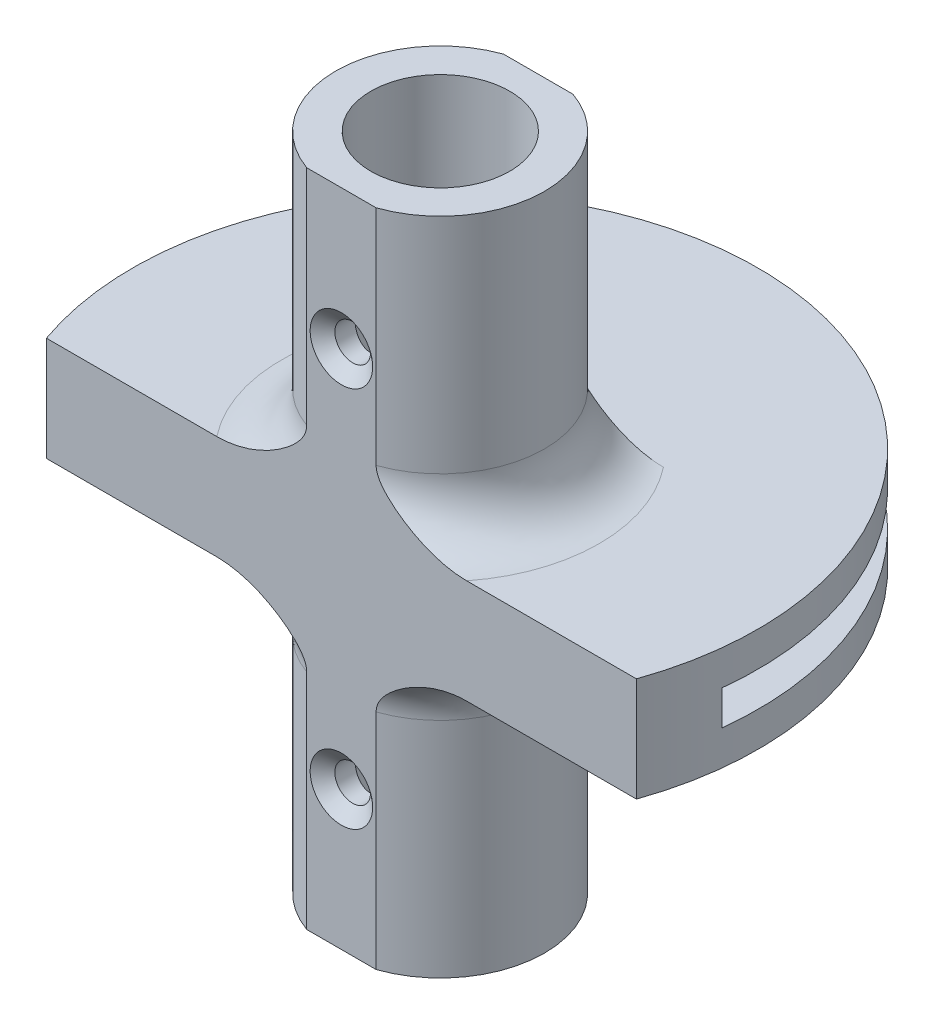
SolidWorks part; units mm, degrees
other "Camera1"
material "ABS"
ref_plane "Front Plane" through (0, 0, 0) normal (0, 0, 1) x (1, 0, 0)
ref_plane "Top Plane" through (0, 0, 0) normal (0, 1, 0) x (1, 0, 0)
ref_plane "Right Plane" through (0, 0, 0) normal (1, 0, 0) x (0, 0, -1)
sketch "Sketch3" plane through (0, 0, 0) normal (0, 1, 0) x (1, 0, 0)
  line L8 (0, 28.6) -> (0, -28.6) construction
  line L9 (0, 28.6) -> (0, -9.5) construction
  line L10 (-26.976, -9.5) -> (26.976, -9.5)
  line L11 (-28.4259, -3.15) -> (28.4259, -3.15)
  arc A4 (26.976, -9.5) -> (-26.976, -9.5) centre (0, 0) ccw
  dimension "D1" = 38.1
  dimension "D2" = 6.35
extrude "Boss-Extrude1" add sketch "Sketch3" along normal blind 3.175 contours L11 A4 | L10 A4 L11
sketch "Sketch18" plane through (0, 0, 0) normal (0, 1, 0) x (1, 0, 0)
  line L0 (7.6093, 9.5806) -> (7.6093, 23.8709)
  line L1 (7.6093, 23.8709) -> (-6.6782, 23.848)
  line L2 (-6.6782, 23.848) -> (-6.6782, 9.5577)
  line L3 (-6.6782, 9.5577) -> (7.6093, 9.5806)
  line L4 (3.4908, 13.6518) -> (3.4908, 19.7615)
  line L5 (3.4908, 19.7615) -> (-4.6572, 19.7686)
  line L6 (-4.6572, 19.7686) -> (-4.6572, 21.7998)
  line L7 (-4.6572, 21.7998) -> (-2.6268, 21.7998)
  line L8 (-2.6268, 21.7998) -> (-2.6269, 11.6094)
  line L9 (-2.6269, 11.6094) -> (-4.6581, 11.6094)
  line L10 (-4.6581, 11.6094) -> (-4.6581, 13.6399)
  line L11 (-4.6581, 13.6399) -> (3.4908, 13.6518)
  spline S0 degree 3 poles (7.6093, 9.5806) (2.8493, 9.573) (-1.9139, 9.5653) (-6.6782, 9.5577) knots 3 3 3 3 4 4 4 4
  spline S1 degree 3 poles (7.6093, 23.8709) (7.6093, 19.1093) (7.6093, 14.3449) (7.6093, 9.5806) knots 2 2 2 2 3 3 3 3
  spline S2 degree 3 poles (-6.6782, 23.848) (-1.9179, 23.8556) (2.8435, 23.8632) (7.6093, 23.8709) knots 1 1 1 1 2 2 2 2
  spline S3 degree 3 poles (-6.6782, 9.5577) (-6.6782, 14.3202) (-6.6782, 19.0827) (-6.6782, 23.848) knots 0 0 0 0 1 1 1 1
  spline S4 degree 3 poles (3.4908, 19.7615) (3.4639, 19.7638) (3.4462, 19.7666) (3.4285, 19.7666) (1.4101, 19.7661) (-0.6084, 19.7654) (-2.6268, 19.7647) knots 12 12 12 12 13 13 13 14 14 14 14
  spline S5 degree 3 poles (3.4908, 13.6518) (3.4908, 15.6921) (3.4908, 17.7258) (3.4908, 19.7615) knots 11 11 11 11 12 12 12 12
  spline S6 degree 3 poles (-2.6269, 13.6437) (-0.6039, 13.6431) (1.419, 13.6424) (3.442, 13.6422) (3.4587, 13.6422) (3.4754, 13.6486) (3.4908, 13.6518) knots 9 9 9 9 10 10 10 11 11 11 11
  spline S7 degree 3 poles (-2.6269, 11.6094) (-2.6269, 12.2941) (-2.6269, 12.9689) (-2.6269, 13.6437) knots 8 8 8 8 9 9 9 9
  spline S8 degree 3 poles (-4.6581, 11.6094) (-3.9766, 11.6094) (-3.3042, 11.6094) (-2.6269, 11.6094) knots 7 7 7 7 8 8 8 8
  spline S9 degree 3 poles (-4.6581, 13.6399) (-4.6581, 12.9525) (-4.6581, 12.2802) (-4.6581, 11.6094) knots 6 6 6 6 7 7 7 7
  spline S10 degree 3 poles (-2.623, 13.6399) (-3.3011, 13.6399) (-3.9791, 13.6399) (-4.6581, 13.6399) knots 5 5 5 5 6 6 6 6
  spline S11 degree 3 poles (-2.6229, 19.7686) (-2.623, 17.7257) (-2.623, 15.6828) (-2.623, 13.6399) knots 4 4 4 4 5 5 5 5
  spline S12 degree 3 poles (-4.6572, 19.7686) (-3.9725, 19.7686) (-3.2977, 19.7686) (-2.6229, 19.7686) knots 3 3 3 3 4 4 4 4
  spline S13 degree 3 poles (-4.6572, 21.7998) (-4.6572, 21.1183) (-4.6572, 20.4459) (-4.6572, 19.7686) knots 2 2 2 2 3 3 3 3
  spline S14 degree 3 poles (-2.6268, 21.7998) (-3.3141, 21.7998) (-3.9864, 21.7998) (-4.6572, 21.7998) knots 1 1 1 1 2 2 2 2
  spline S15 degree 3 poles (-2.6268, 19.7647) (-2.6268, 20.4427) (-2.6268, 21.1208) (-2.6268, 21.7998) knots 0 0 0 0 1 1 1 1
sketch "Sketch19" plane through (0, 0, 0) normal (0, 1, 0) x (1, 0, 0)
  line L3 (-3.175, 8.4947) -> (3.175, 8.4947)
  line L4 (-3.175, -9.5) -> (3.175, -9.5)
  arc A3 (3.175, -9.5) -> (3.175, 8.4947) centre (0.0442, -0.5026) ccw
  arc A4 (-3.175, 8.4947) -> (-3.175, -9.5) centre (0.0442, -0.5026) ccw
  circle A5 centre (0.0442, -0.5026) radius 6.35
  point P10 (0, 8.4947)
  point P11 (0, -9.5)
  dimension "D1" = 12.7
  dimension "D2" = 3.1765
  dimension "D3" = 3.2059
  dimension "D4" = 6.35
extrude "Boss-Extrude2" add sketch "Sketch19" against normal blind 25.4 contours L3 A4 A5 | L3 A5 L4 A3 region at (0, 0, -8.2324)
ref_plane "Plane2" through (0, 3.175, 0) normal (0, 1, 0) x (1, 0, 0)
sketch "Sketch20" plane through (0, 3.175, 0) normal (0, 1, 0) x (1, 0, 0)
  line L0 (-28.4259, -3.15) -> (28.4259, -3.15) construction
  line L1 (-26.976, -9.5) -> (26.976, -9.5) construction
  line L2 (-28.4259, -3.15) -> (28.4259, -3.15)
  line L3 (-26.976, -9.5) -> (26.976, -9.5)
  arc A0 (26.976, -9.5) -> (-26.976, -9.5) centre (0, 0) ccw construction
  arc A1 (26.976, -9.5) -> (28.4259, -3.15) centre (0, 0) ccw
  arc A2 (-28.4259, -3.15) -> (-26.976, -9.5) centre (0, 0) ccw
extrude "Boss-Extrude3" add sketch "Sketch20" along normal blind 3.175
ref_plane "Plane3" through (0, 6.35, 0) normal (0, 1, 0) x (1, 0, 0)
sketch "Sketch21" plane through (0, 6.35, 0) normal (0, 1, 0) x (1, 0, 0)
  line L0 (-26.976, -9.5) -> (26.976, -9.5)
  arc A0 (26.976, -9.5) -> (-26.976, -9.5) centre (0, 0) ccw construction
  arc A1 (26.976, -9.5) -> (-26.976, -9.5) centre (0, 0) ccw
extrude "Boss-Extrude4" add sketch "Sketch21" along normal blind 3.175
ref_plane "Plane4" through (0, 9.525, 0) normal (0, 1, 0) x (1, 0, 0)
sketch "Sketch23" plane through (0, 9.525, 0) normal (0, 1, 0) x (1, 0, 0)
  line L0 (-26.976, -9.5) -> (26.976, -9.5) construction
  line L1 (-3.175, 8.4947) -> (3.175, 8.4947) construction
  line L2 (-3.175, -9.5) -> (3.175, -9.5)
  line L3 (-3.175, 8.4947) -> (3.175, 8.4947)
  circle A0 centre (0.0442, -0.5026) radius 6.35 construction
  arc A1 (-3.175, 8.4947) -> (-3.175, -9.5) centre (0.0442, -0.5026) ccw construction
  arc A2 (3.175, -9.5) -> (3.175, 8.4947) centre (0.0442, -0.5026) ccw construction
  circle A3 centre (0.0442, -0.5026) radius 6.35
  arc A4 (-3.175, 8.4947) -> (-3.175, -9.5) centre (0.0442, -0.5026) ccw
  arc A5 (3.175, -9.5) -> (3.175, 8.4947) centre (0.0442, -0.5026) ccw
extrude "Boss-Extrude5" add sketch "Sketch23" along normal blind 25.4
hole_wizard "CSK for #4 Flat Head Machine Screw (100)1" positions "Sketch24" profile "Sketch25" countersink size "#4" standard "ANSI Inch" end condition up to next
sketch "Sketch24" plane through (0, 0, 9.5) normal (0, 0, 1) x (1, 0, 0)
  line L4 (0, -25.4) -> (0, 0) construction
  line L5 (-3.175, -25.4) -> (3.175, -25.4) construction
  line L7 (0, 9.433) -> (0, 34.925) construction
  line L8 (-3.175, 34.925) -> (3.175, 34.925) construction
  point P0 (0, -12.7)
  point P2 (0, 22.179)
sketch "Sketch25" plane through (0, -12.7, 9.5) normal (1, 0, 0) x (0, -1, 0)
  line L0 (0, 0) -> (0, 2.6475)
  line L1 (0, 2.6475) -> (1.6319, 2.6475)
  line L2 (1.6319, 2.6475) -> (1.6319, 1.0284)
  line L3 (1.6319, 1.0284) -> (2.8575, 0)
  line L5 (2.8575, 0) -> (0, 0)
  line L6 (-1.632, 1.0284) -> (-2.8575, 0) construction
  line L11 (0, -6.35) -> (0, 107.95) construction
  dimension "Thru Hole Dia." = 3.2639
  dimension "Thru Hole Depth" = 2.6475
  dimension "Near C'Sink Dia." = 5.715
  dimension "Near C'Sink Angle" = 100
hole_wizard "CSK for #4 Flat Head Machine Screw (100)2" positions "Sketch26" profile "Sketch27" countersink size "#4" standard "ANSI Inch" end condition up to next
sketch "Sketch26" plane through (0, 0, 0) normal (0, -1, 0) x (-1, 0, 0)
  line L3 (27.0462, 9.2981) -> (0, 9.2981) construction
  line L4 (0, 9.2981) -> (-27.0462, 9.2981) construction
  line L7 (0, 28.6) -> (0, -28.6) construction
  arc A0 (26.976, -9.5) -> (-26.976, -9.5) centre (0, 0) ccw construction
  arc A1 (26.976, -9.5) -> (-26.976, -9.5) centre (0, 0) ccw
  point P0 (13.5231, 9.2981)
  point P2 (-13.5231, 9.2981)
sketch "Sketch27" plane through (-13.5231, 0, -9.2981) normal (1, 0, 0) x (0, 0, -1)
  line L0 (0, 0) -> (0, 3.175)
  line L1 (0, 3.175) -> (1.6319, 3.175)
  line L2 (1.6319, 3.175) -> (1.6319, 1.0284)
  line L3 (1.6319, 1.0284) -> (2.8575, 0)
  line L5 (2.8575, 0) -> (0, 0)
  line L6 (-1.6319, 1.0284) -> (-2.8575, 0) construction
  line L11 (0, -6.35) -> (0, 107.95) construction
  dimension "Thru Hole Dia." = 3.2639
  dimension "Thru Hole Depth" = 3.175
  dimension "Near C'Sink Dia." = 5.715
  dimension "Near C'Sink Angle" = 100
fillet "Fillet1" radius 5 4 edges at (-9.5117, 0, 0.5026) (9.5707, 0, 0.5026) (-9.5117, 9.525, 0.5026) (9.5707, 9.525, 0.5026)
sketch "Sketch28" plane through (0, 9.525, 0) normal (0, 1, 0) x (1, 0, 0)
  line L0 (-4.6581, 11.6094) -> (-4.6581, 13.6399) construction
  line L1 (-4.6581, 13.6399) -> (3.4908, 13.6518) construction
  line L2 (-2.6269, 11.6094) -> (-4.6581, 11.6094) construction
  line L3 (-2.6268, 21.7998) -> (-2.6269, 11.6094) construction
  line L4 (-4.6572, 21.7998) -> (-2.6268, 21.7998) construction
  line L5 (-4.6572, 19.7686) -> (-4.6572, 21.7998) construction
  line L6 (3.4908, 19.7615) -> (-4.6572, 19.7686) construction
  line L7 (3.4908, 13.6518) -> (3.4908, 19.7615) construction
  line L8 (-6.6782, 23.848) -> (-6.6782, 9.5577) construction
  line L9 (-6.6782, 9.5577) -> (7.6093, 9.5806) construction
  line L10 (7.6093, 23.8709) -> (-6.6782, 23.848) construction
  line L11 (7.6093, 9.5806) -> (7.6093, 23.8709) construction
  line L12 (-4.6581, 11.6094) -> (-4.6581, 13.6399)
  line L13 (-4.6581, 13.6399) -> (3.4908, 13.6518)
  line L14 (-2.6269, 11.6094) -> (-4.6581, 11.6094)
  line L15 (-2.6268, 21.7998) -> (-2.6269, 11.6094)
  line L16 (-4.6572, 21.7998) -> (-2.6268, 21.7998)
  line L17 (-4.6572, 19.7686) -> (-4.6572, 21.7998)
  line L18 (3.4908, 19.7615) -> (-4.6572, 19.7686)
  line L19 (3.4908, 13.6518) -> (3.4908, 19.7615)
  line L20 (-6.6782, 23.848) -> (-6.6782, 9.5577)
  line L21 (-6.6782, 9.5577) -> (7.6093, 9.5806)
  line L22 (7.6093, 23.8709) -> (-6.6782, 23.848)
  line L23 (7.6093, 9.5806) -> (7.6093, 23.8709)
  line L24 (-6.6782, 23.848) -> (-6.6782, 9.5577)
  line L25 (-6.6782, 9.5577) -> (-6.6157, 9.5578)
  line L26 (-6.6157, 9.5578) -> (7.6093, 9.5806)
  line L27 (7.6093, 9.5806) -> (7.6093, 23.8709)
  line L28 (7.6093, 23.8709) -> (-6.6782, 23.848)
  line L29 (-4.6572, 21.7998) -> (-4.6572, 19.7686)
  line L30 (3.4908, 19.7615) -> (-4.6572, 19.7686)
  line L31 (3.4908, 19.7615) -> (3.4908, 13.6518)
  line L32 (3.4908, 13.6518) -> (-4.6581, 13.6399)
  line L33 (-4.6581, 13.6399) -> (-4.6581, 11.6094)
  line L34 (-4.6581, 11.6094) -> (-2.6269, 11.6094)
  line L35 (-2.6269, 11.6094) -> (-2.6268, 21.7998)
  line L36 (-2.6268, 21.7998) -> (-4.6572, 21.7998)
  line L37 (-4.6572, 19.7686) -> (-2.6268, 19.7647)
  line L38 (3.4908, 19.7615) -> (3.4908, 13.6518)
  spline S0 degree 3 poles (-4.6581, 2013.5668) (-4.6581, -1850.1642) (-4.6581, 1872.1418) (-4.6581, -1988.3408) knots -45.012058 -45.012058 -45.012058 -45.012058 59.225344 59.225344 59.225344 59.225344 only from (-4.6581, 13.6399) to (-4.6581, 11.6094) construction
  spline S1 degree 3 poles (1997.3464, 13.6399) (-1669.3435, 13.6399) (1664.649, 13.6399) (-2004.6114, 13.6399) knots -118.121507 -118.121507 -118.121507 -118.121507 128.166269 128.166269 128.166269 128.166269 only from (-2.623, 13.6399) to (-4.6581, 13.6399) construction
  spline S2 degree 3 poles (149.124, 2011.6105) (-154.6718, 254.6636) (149.774, -218.2181) (-155.4142, -1978.1045) knots -268.743619 -268.743619 -268.743619 -268.743619 277.367974 277.367974 277.367974 277.367974 only from (-2.6229, 19.7686) to (-2.623, 13.6399) construction
  spline S3 degree 3 poles (-2004.6255, 19.7686) (1843.4202, 19.7686) (-1848.0418, 19.7686) (1997.3426, 19.7686) knots -53.527865 -53.527865 -53.527865 -53.527865 61.507559 61.507559 61.507559 61.507559 only from (-4.6572, 19.7686) to (-2.6229, 19.7686) construction
  spline S4 degree 3 poles (-2004.6283, 11.6094) (1859.2549, 11.6094) (-1865.7411, 11.6094) (1997.2866, 11.6094) knots -43.59336 -43.59336 -43.59336 -43.59336 58.880399 58.880399 58.880399 58.880399 only from (-4.6581, 11.6094) to (-2.6269, 11.6094) construction
  spline S5 degree 3 poles (-919.4379, -1684.6171) (-609.8911, 24.5643) (-303.2293, 13.6711) (3.442, 13.6422) (4.4398, 13.6422) (5.4377, 36.4051) (-271.9776, -1967.2394) knots -141.596136 -141.596136 -141.596136 -141.596136 10 10 10 69.67338 69.67338 69.67338 69.67338 only from (-2.6269, 13.6437) to (3.4908, 13.6518) construction
  spline S6 degree 3 poles (-2.6269, -1988.3677) (-2.6269, 1859.7154) (-2.6269, -1831.8037) (-2.6269, 2013.6181) knots -48.520466 -48.520466 -48.520466 -48.520466 66.500162 66.500162 66.500162 66.500162 only from (-2.6269, 11.6094) to (-2.6269, 13.6437) construction
  spline S7 degree 3 poles (1997.371, 21.7998) (-1866.4491, 21.7998) (1855.8734, 21.7998) (-2004.5981, 21.7998) knots -50.020453 -50.020453 -50.020453 -50.020453 54.231218 54.231218 54.231218 54.231218 only from (-2.6268, 21.7998) to (-4.6572, 21.7998) construction
  spline S8 degree 3 poles (1894.5892, 670.5375) (5.5073, 10.0448) (4.4693, 19.7669) (3.4285, 19.7666) (-373.7493, 19.6738) (-750.9271, 12.2844) (-1225.6923, 1483.0937) knots -45.843923 -45.843923 -45.843923 -45.843923 13 13 13 199.867967 199.867967 199.867967 199.867967 only from (3.4908, 19.7615) to (-2.6268, 19.7647) construction
  spline S9 degree 3 poles (-2.6268, -1980.2048) (-2.6268, 1687.9047) (-2.6268, -1648.9211) (-2.6268, 2021.7382) knots -122.596234 -122.596234 -122.596234 -122.596234 122.641297 122.641297 122.641297 122.641297 only from (-2.6268, 19.7647) to (-2.6268, 21.7998) construction
  spline S10 degree 3 poles (-4.6572, 2021.7847) (-4.6572, -1842.16) (-4.6572, 1882.9352) (-4.6572, -1980.1647) knots -48.58167 -48.58167 -48.58167 -48.58167 53.867194 53.867194 53.867194 53.867194 only from (-4.6572, 21.7998) to (-4.6572, 19.7686) construction
  spline S11 degree 3 poles (3.4908, -1986.3327) (3.4908, 1554.6009) (3.4908, -1517.1831) (3.4908, 2019.6866) knots -45.633829 -45.633829 -45.633829 -45.633829 69.122677 69.122677 69.122677 69.122677 only from (3.4908, 13.6518) to (3.4908, 19.7615) construction
  spline S12 degree 3 poles (-1992.3266, 6.3737) (4251.6377, 16.3859) (-4295.809, 2.68) (1993.2472, 12.7646) knots -114.993612 -114.993612 -114.993612 -114.993612 124.360748 124.360748 124.360748 124.360748 only from (7.6093, 9.5806) to (-6.6782, 9.5577) construction
  spline S13 degree 3 poles (-6.6782, -1990.4192) (-6.6782, 665.303) (-6.6782, -646.1204) (-6.6782, 2023.8195) knots -70.812631 -70.812631 -70.812631 -70.812631 71.066115 71.066115 71.066115 71.066115 only from (-6.6782, 9.5577) to (-6.6782, 23.848) construction
  spline S14 degree 3 poles (-2006.6452, 20.641) (711.2092, 24.9991) (-734.1394, 22.6815) (2007.5478, 27.0778) knots -66.584962 -66.584962 -66.584962 -66.584962 68.331775 68.331775 68.331775 68.331775 only from (-6.6782, 23.848) to (7.6093, 23.8709) construction
  spline S15 degree 3 poles (7.6093, -1976.105) (7.6093, 4061.8895) (7.6093, -4050.7067) (7.6093, 2009.4941) knots -105.193473 -105.193473 -105.193473 -105.193473 111.363259 111.363259 111.363259 111.363259 only from (7.6093, 23.8709) to (7.6093, 9.5806) construction
  spline S16 degree 3 poles (-4.6581, 13.6399) (-4.6581, 12.9525) (-4.6581, 12.2802) (-4.6581, 11.6094) knots 6 6 6 6 7 7 7 7
  spline S17 degree 3 poles (-2.623, 13.6399) (-3.3011, 13.6399) (-3.9791, 13.6399) (-4.6581, 13.6399) knots 5 5 5 5 6 6 6 6
  spline S18 degree 3 poles (-2.6229, 19.7686) (-2.623, 17.7257) (-2.623, 15.6828) (-2.623, 13.6399) knots 4 4 4 4 5 5 5 5
  spline S19 degree 3 poles (-4.6572, 19.7686) (-3.9725, 19.7686) (-3.2977, 19.7686) (-2.6229, 19.7686) knots 3 3 3 3 4 4 4 4
  spline S20 degree 3 poles (-4.6581, 11.6094) (-3.9766, 11.6094) (-3.3042, 11.6094) (-2.6269, 11.6094) knots 7 7 7 7 8 8 8 8
  spline S21 degree 3 poles (-2.6269, 13.6437) (-0.6039, 13.6431) (1.419, 13.6424) (3.442, 13.6422) (3.4587, 13.6422) (3.4754, 13.6486) (3.4908, 13.6518) knots 9 9 9 9 10 10 10 11 11 11 11
  spline S22 degree 3 poles (-2.6269, 11.6094) (-2.6269, 12.2941) (-2.6269, 12.9689) (-2.6269, 13.6437) knots 8 8 8 8 9 9 9 9
  spline S23 degree 3 poles (-2.6268, 21.7998) (-3.3141, 21.7998) (-3.9864, 21.7998) (-4.6572, 21.7998) knots 1 1 1 1 2 2 2 2
  spline S24 degree 3 poles (3.4908, 19.7615) (3.4639, 19.7638) (3.4462, 19.7666) (3.4285, 19.7666) (1.4101, 19.7661) (-0.6084, 19.7654) (-2.6268, 19.7647) knots 12 12 12 12 13 13 13 14 14 14 14
  spline S25 degree 3 poles (-2.6268, 19.7647) (-2.6268, 20.4427) (-2.6268, 21.1208) (-2.6268, 21.7998) knots 0 0 0 0 1 1 1 1
  spline S26 degree 3 poles (-4.6572, 21.7998) (-4.6572, 21.1183) (-4.6572, 20.4459) (-4.6572, 19.7686) knots 2 2 2 2 3 3 3 3
  spline S27 degree 3 poles (3.4908, 13.6518) (3.4908, 15.6921) (3.4908, 17.7258) (3.4908, 19.7615) knots 11 11 11 11 12 12 12 12
  spline S28 degree 3 poles (7.6093, 9.5806) (2.8493, 9.573) (-1.9139, 9.5653) (-6.6782, 9.5577) knots 3 3 3 3 4 4 4 4
  spline S29 degree 3 poles (-6.6782, 9.5577) (-6.6782, 14.3202) (-6.6782, 19.0827) (-6.6782, 23.848) knots 0 0 0 0 1 1 1 1
  spline S30 degree 3 poles (-6.6782, 23.848) (-1.9179, 23.8556) (2.8435, 23.8632) (7.6093, 23.8709) knots 1 1 1 1 2 2 2 2
  spline S31 degree 3 poles (7.6093, 23.8709) (7.6093, 19.1093) (7.6093, 14.3449) (7.6093, 9.5806) knots 2 2 2 2 3 3 3 3
extrude "Cut-Extrude1" [suppressed] cut sketch "Sketch28" against normal blind 1 contours L21 L23 L22 L20 S25 S19 S18 L30 S24 L19 S21 L32 S17 L35 L14 L12 L13 S22 L37 L17 L16
